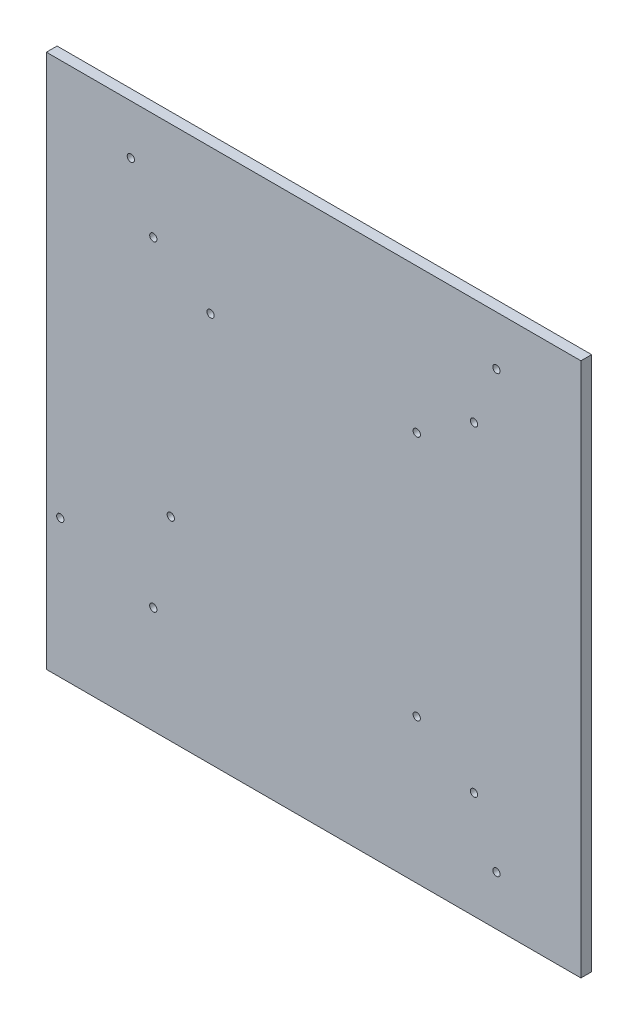
SolidWorks part; units mm, degrees
material "5052-H34"
ref_plane "正面" through (0, 0, 0) normal (0, 0, 1) x (1, 0, 0)
ref_plane "平面" through (0, 0, 0) normal (0, 1, 0) x (1, 0, 0)
ref_plane "右側面" through (0, 0, 0) normal (1, 0, 0) x (0, 0, -1)
sketch "ｽｹｯﾁ1" plane through (0, 0, 0) normal (0, 0, 1) x (1, 0, 0)
  line L1 (-250, -250) -> (250, -250)
  line L2 (-250, -250) -> (-250, 250)
  line L3 (-250, 250) -> (250, 250)
  line L4 (250, -250) -> (250, 250)
  line L5 (-250, -250) -> (250, 250) construction
  line L6 (-250, 250) -> (250, -250) construction
  point P0 (0, 0)
  dimension "D1" = 500
  dimension "D2" = 500
extrude "ﾎﾞｽ - 押し出し1" add sketch "ｽｹｯﾁ1" along normal blind 10
ref_axis "軸1" through (0, 0, -0.5) along (0, 0, 1)
sketch "ｽｹｯﾁ10" plane through (0, 0, 10) normal (0, 0, 1) x (1, 0, 0)
  line L1 (-150, -150) -> (150, -150) construction
  line L2 (-150, -150) -> (-150, 150) construction
  line L3 (-150, 150) -> (150, 150) construction
  line L4 (150, -150) -> (150, 150) construction
  line L5 (-150, -150) -> (150, 150) construction
  line L6 (-150, 150) -> (150, -150) construction
  point P0 (0, 0)
  dimension "D1" = 300
hole_wizard "M8x1.25 ねじ穴2" positions "3Dｽｹｯﾁ3" profile "ｽｹｯﾁ11" tap size "M8x1.25" standard "JIS" end condition through all
sketch3d "3Dｽｹｯﾁ3"
  point P0 (-150, 150, 10)
  point P3 (150, 150, 10)
  point P6 (-150, -150, 10)
  point P9 (150, -150, 10)
sketch "ｽｹｯﾁ11" plane through (-150, 150, 10) normal (1, 0, 0) x (0, -1, 0)
  line L0 (0, 0) -> (0, 10)
  line L1 (0, 10) -> (3.4, 10)
  line L2 (3.4, 10) -> (3.4, 0)
  line L5 (3.4, 0) -> (0, 0)
  line L11 (0, -6.35) -> (0, 107.95) construction
  dimension "次ｻｰﾌｪｽまでのねじ下穴ﾄﾞﾘﾙ直径" = 6.8
  dimension "次ｻｰﾌｪｽまでのねじ下穴ﾄﾞﾘﾙの深さ" = 10
cosmetic thread "穴のねじ山6" parameters "D2"=8
cosmetic thread "穴のねじ山7" parameters "D2"=8
cosmetic thread "穴のねじ山8" parameters "D2"=8
cosmetic thread "穴のねじ山9" parameters "D2"=8
sketch "ｽｹｯﾁ12" plane through (0, 0, 10) normal (0, 0, 1) x (1, 0, 0)
  line L0 (0, 0) -> (-133.651, -68.0986)
  line L1 (0, 0) -> (-96.4181, 114.9067)
  line L2 (0, 0) -> (96.4181, 114.9067)
  line L3 (0, 0) -> (96.4181, -114.9067)
  line L4 (0, 196.2728) -> (0, -187.021) construction
  line L5 (0, 0) -> (170.9815, 203.7678)
  line L6 (0, 0) -> (-170.9815, 203.7678)
  line L7 (0, 0) -> (-237.0077, -120.7615)
  line L8 (0, 0) -> (170.9815, -203.7678)
  circle A0 centre (0, 0) radius 150
  circle A1 centre (0, 0) radius 266
  dimension "D1" = 300
  dimension "D6" = 532
  dimension "D2" = 40
  dimension "D3" = 40
  dimension "D4" = 63
  dimension "D5" = 40
hole_wizard "M8x1.25 ねじ穴1" positions "3Dｽｹｯﾁ4" profile "ｽｹｯﾁ13" tap size "M8x1.25" standard "JIS" end condition through all
sketch3d "3Dｽｹｯﾁ4"
  point P0 (-96.4181, 114.9067, 10)
  point P3 (96.4181, 114.9067, 10)
  point P6 (96.4181, -114.9067, 10)
  point P9 (-133.651, -68.0986, 10)
  point P13 (-170.9815, 203.7678, 10)
  point P16 (170.9815, 203.7678, 10)
  point P19 (-237.0077, -120.7615, 10)
  point P22 (170.9815, -203.7678, 10)
sketch "ｽｹｯﾁ13" plane through (-96.4181, 114.9067, 10) normal (1, 0, 0) x (0, -1, 0)
  line L0 (0, 0) -> (0, 10)
  line L1 (0, 10) -> (3.4, 10)
  line L2 (3.4, 10) -> (3.4, 0)
  line L5 (3.4, 0) -> (0, 0)
  line L11 (0, -6.35) -> (0, 107.95) construction
  dimension "次ｻｰﾌｪｽまでのねじ下穴ﾄﾞﾘﾙ直径" = 6.8
  dimension "次ｻｰﾌｪｽまでのねじ下穴ﾄﾞﾘﾙの深さ" = 10
cosmetic thread "穴のねじ山10" parameters "D2"=8
cosmetic thread "穴のねじ山11" parameters "D2"=8
cosmetic thread "穴のねじ山12" parameters "D2"=8
cosmetic thread "穴のねじ山13" parameters "D2"=8
cosmetic thread "穴のねじ山14" parameters "D2"=8
cosmetic thread "穴のねじ山15" parameters "D2"=8
cosmetic thread "穴のねじ山16" parameters "D2"=8
cosmetic thread "穴のねじ山17" parameters "D2"=8
ref_axis "中心軸" through (0, 0, -101.7257) along (0, 0, 1)
